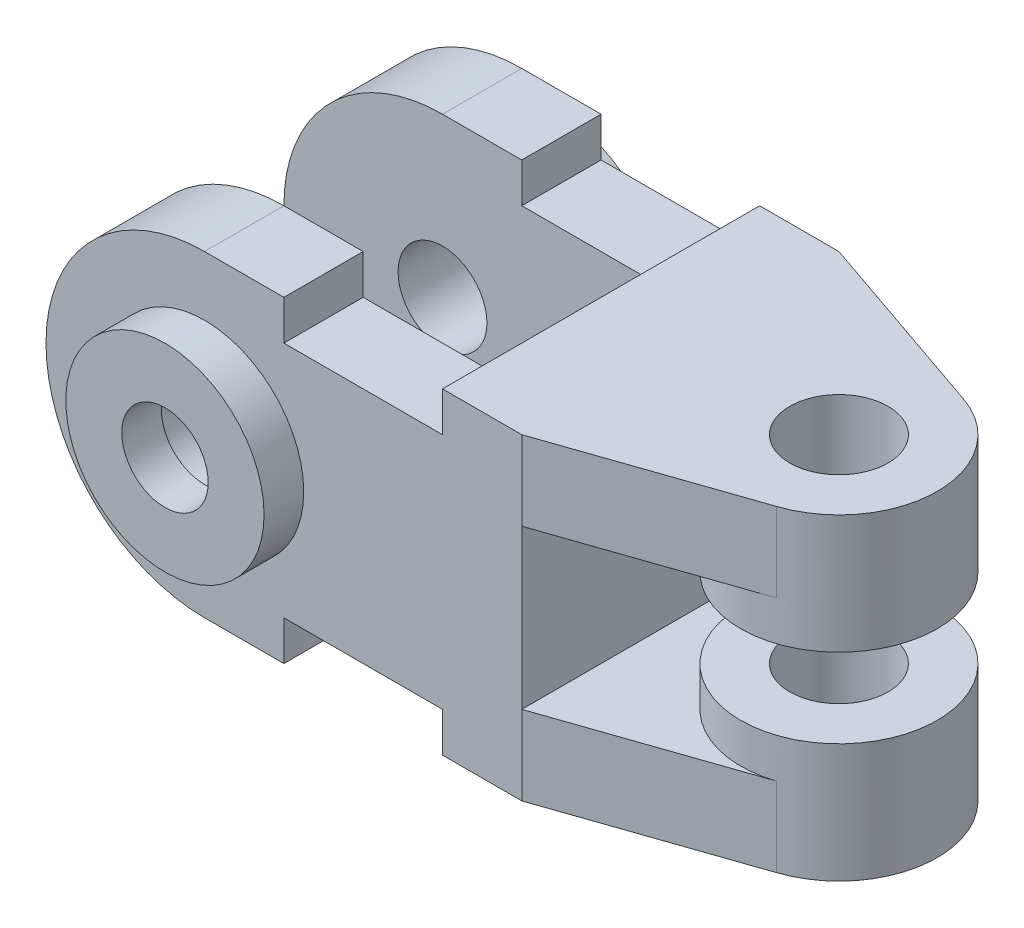
SolidWorks part; units mm, degrees
ref_plane "Front Plane" through (0, 0, 0) normal (0, 0, 1) x (1, 0, 0)
ref_plane "Top Plane" through (0, 0, 0) normal (0, 1, 0) x (1, 0, 0)
ref_plane "Right Plane" through (0, 0, 0) normal (1, 0, 0) x (0, 0, -1)
sketch "Sketch1" plane through (0, 0, 0) normal (0, 1, 0) x (1, 0, 0)
  line L0 (-60.0135, 26.0693) -> (16.1865, 26.0693)
  line L1 (-60.0135, 26.0693) -> (-60.0135, 13.3693)
  line L2 (-60.0135, -24.7307) -> (16.1865, -24.7307)
  line L5 (-60.0135, 0.6693) -> (24.1823, 0.6693) construction
  line L6 (16.1865, 26.0693) -> (16.1865, -24.7307) construction
  line L7 (16.1865, 26.0693) -> (46.713, 15.5595)
  line L8 (3.4865, 13.3693) -> (3.4865, -12.0307)
  line L9 (-60.0135, 13.3693) -> (3.4865, 13.3693)
  line L10 (-60.0135, -12.0307) -> (3.4865, -12.0307)
  line L11 (16.1865, -24.7307) -> (46.553, -14.275)
  line L12 (24.1823, 0.6693) -> (41.5865, 0.6693) construction
  line L13 (-60.0135, -12.0307) -> (-60.0135, -24.7307)
  arc A2 (46.713, 15.5595) -> (46.553, -14.275) centre (41.5865, 0.6693) cw
  circle A3 centre (41.5865, 0.6693) radius 7.874
  dimension "D3" = 25.4
  dimension "D5" = 15.748
  dimension "D9" = 15.748
  dimension "D1" = 76.2
  dimension "D2" = 50.8
  dimension "D4" = 25.4
  dimension "D6" = 12.7
  dimension "D7" = 12.7
  dimension "D8" = 12.7
extrude "Boss-Extrude1" add sketch "Sketch1" along normal blind 50.8
sketch "Sketch2" plane through (0, 0, 24.7307) normal (0, 0, 1) x (1, 0, 0)
  line L0 (-60.0135, 25.4) -> (-34.6135, 25.4) construction
  line L1 (-60.0135, 50.8) -> (-60.0135, 0) construction
  line L2 (-34.6135, 50.8) -> (-60.0135, 50.8)
  line L3 (-60.0135, 50.8) -> (-60.0135, 25.4)
  line L4 (-60.0135, 25.4) -> (-60.0135, 0)
  line L5 (-60.0135, 0) -> (-34.6135, 0)
  line L6 (-21.9135, 50.8) -> (-21.9135, 44.45)
  line L7 (-60.0135, 50.8) -> (16.1865, 50.8) construction
  line L8 (-21.9135, 44.45) -> (3.4865, 44.45)
  line L9 (3.4865, 44.45) -> (3.4865, 50.8)
  line L10 (-21.9135, 0) -> (-21.9135, 6.35)
  line L11 (-60.0135, 0) -> (16.1865, 0) construction
  line L12 (-21.9135, 6.35) -> (3.4865, 6.35)
  line L13 (3.4865, 6.35) -> (3.4865, 0)
  line L14 (-21.9135, 50.8) -> (3.4865, 50.8)
  line L15 (-21.9135, 0) -> (3.4865, 0)
  line L16 (16.1865, 38.1) -> (16.1865, 12.7)
  line L17 (16.1865, 50.8) -> (16.1865, 0) construction
  line L18 (16.1865, 12.7) -> (65.7547, 12.7)
  line L19 (65.7547, 12.7) -> (65.7547, 38.1)
  line L20 (65.7547, 38.1) -> (16.1865, 38.1)
  line L21 (16.1865, 50.8) -> (46.553, 50.8) construction
  line L22 (16.1865, 0) -> (46.553, 0) construction
  arc A0 (-34.6135, 50.8) -> (-34.6135, 0) centre (-34.6135, 25.4) ccw
  circle A1 centre (-34.6135, 25.4) radius 7.112
  line M10 (-60.0135, 0) -> (16.1865, 0)
  line M11 (16.1865, 0) -> (16.1865, 50.8)
  line M12 (16.1865, 50.8) -> (-60.0135, 50.8)
  line M13 (-60.0135, 50.8) -> (-60.0135, 0)
  dimension "D2" = 14.224
  dimension "D1" = 25.4
  dimension "D3" = 25.4
  dimension "D4" = 6.35
  dimension "D5" = 6.35
  dimension "D6" = 12.7
  dimension "D7" = 12.7
extrude "Cut-Extrude1" cut sketch "Sketch2" against normal blind 86.106 contours L8 L9 L6 M12 | A1 | L13 L12 L10 M10 | L19 L20 L18 M11 | A0 M12 M13 | A0 M13 M10 region at (-54.3399, 45.1265, 24.7307) region at (-54.3399, 5.6735, 24.7307) region at (-9.2135, 47.625, 24.7307) region at (-9.2135, 3.175, 24.7307) region at (40.9706, 25.4, 24.7307) region at (-34.6135, 25.4, 24.7307)
sketch "Sketch3" plane through (0, 0, 24.7307) normal (0, 0, 1) x (1, 0, 0)
  circle A0 centre (-34.6135, 25.4) radius 15.875
  circle A1 centre (-34.6135, 25.4) radius 6.9214
  dimension "D1" = 31.75
extrude "Boss-Extrude2" add sketch "Sketch3" along normal blind 6.35
sketch "Sketch4" plane through (0, 0, -26.0693) normal (0, 0, -1) x (-1, 0, 0)
  circle A0 centre (34.6135, 25.4) radius 15.875
  circle A1 centre (34.6135, 25.4) radius 7.112
  circle A2 centre (34.6135, 25.4) radius 7.112 construction
  dimension "D1" = 31.75
extrude "Boss-Extrude3" add sketch "Sketch4" along normal blind 6.35
sketch "Sketch5" plane through (0, 12.7, 0) normal (0, 1, 0) x (1, 0, 0)
  circle A0 centre (41.5865, 0.6693) radius 7.874
  circle A1 centre (41.5865, 0.6693) radius 15.748
  arc A2 (46.553, -14.275) -> (46.713, 15.5595) centre (41.5865, 0.6693) ccw construction
  circle A3 centre (41.5865, 0.6693) radius 7.874 construction
extrude "Boss-Extrude4" add sketch "Sketch5" along normal blind 6.35
sketch "Sketch6" plane through (0, 38.1, 0) normal (0, -1, 0) x (1, 0, 0)
  circle A0 centre (41.5865, -0.6693) radius 7.874
  circle A1 centre (41.5865, -0.6693) radius 15.748
  arc A2 (46.713, -15.5595) -> (46.553, 14.275) centre (41.5865, -0.6693) ccw construction
extrude "Boss-Extrude5" add sketch "Sketch6" along normal blind 6.35
